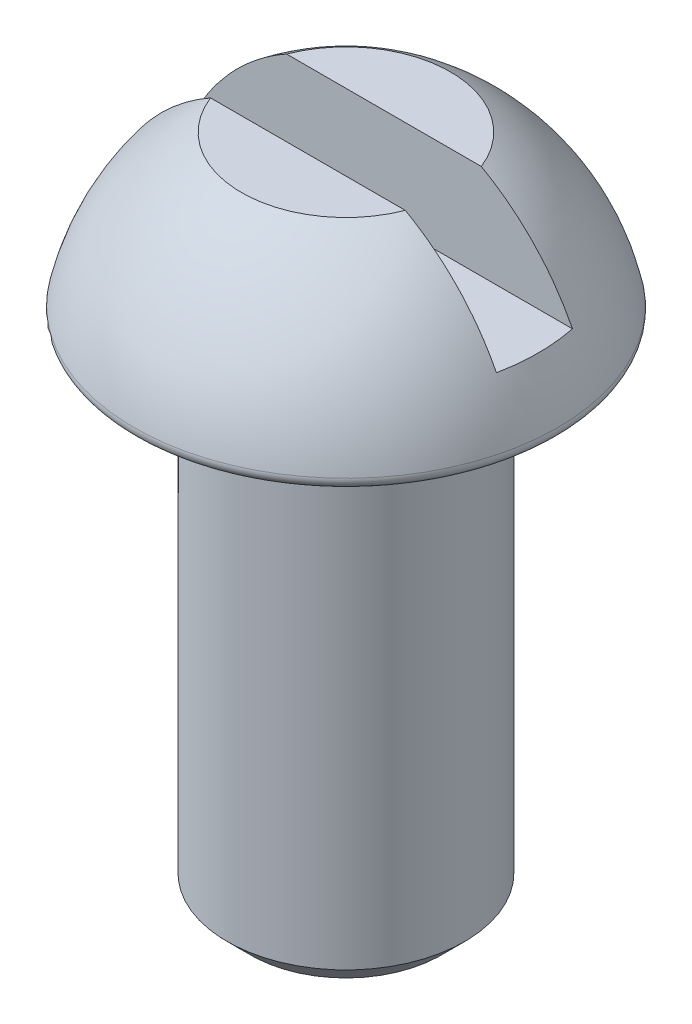
SolidWorks part; units mm, degrees
ref_plane "Спереди" through (0, 0, 0) normal (0, 0, 1) x (1, 0, 0)
ref_plane "Сверху" through (0, 0, 0) normal (0, 1, 0) x (1, 0, 0)
ref_plane "Справа" through (0, 0, 0) normal (1, 0, 0) x (0, 0, -1)
sketch "Эскиз1" plane through (0, 0, 0) normal (0, 0, 1) x (1, 0, 0)
  line L0 (2.25, 5.3) -> (1.25, 5.3)
  line L1 (0, 0) -> (0, 7)
  line L2 (1.25, 5.3) -> (1.25, 0.25)
  line L3 (1.25, 0.25) -> (1, 0)
  line L4 (1, 0) -> (0, 0)
  line L5 (0, 7) -> (1.1, 7)
  arc A0 (1.1, 7) -> (2.25, 5.3) centre (-0.1634, 4.9064) cw
  dimension "D2" = 1.1
  dimension "D8" = 2.1
  dimension "D1" = 7
  dimension "D3" = 1.25
  dimension "D4" = 1
  dimension "D5" = 1.7
  dimension "D6" = 2.25
  dimension "D7" = 45
  dimension "D9" = 1.25
revolve "Повернуть1" add sketch "Эскиз1" angle 360 about L1
fillet "Скругление1" radius 0.1 1 edges at (0, 5.3, -2.25)
sketch "Эскиз3" plane through (0, 7, 0) normal (0, 1, 0) x (-1, 0, 0)
  line L1 (2.5, -0.4) -> (-2.5, -0.4)
  line L2 (2.5, -0.4) -> (2.5, 0.4)
  line L3 (2.5, 0.4) -> (-2.5, 0.4)
  line L4 (-2.5, -0.4) -> (-2.5, 0.4)
  dimension "D1" = 0.8
  dimension "D2" = 0.4
  dimension "D3" = 5
  dimension "D4" = 2.5
extrude "Вырез-Вытянуть2" cut sketch "Эскиз3" against normal blind 1
ref_axis "Ось1" through (0, -104.1565, 0) along (0, 1, 0)
